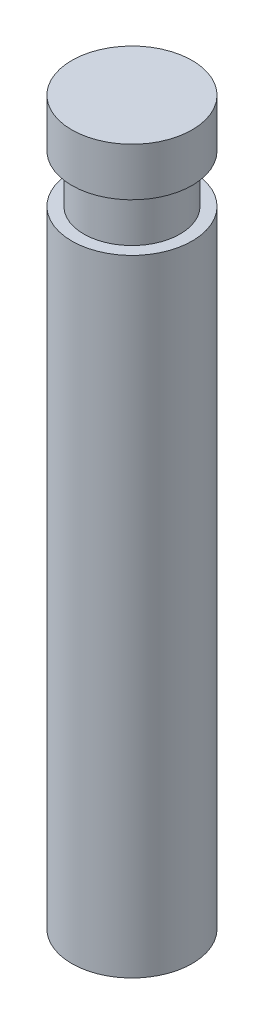
SolidWorks part; units mm, degrees
ref_plane "Front Plane" through (0, 0, 0) normal (0, 0, 1) x (1, 0, 0)
ref_plane "Top Plane" through (0, 0, 0) normal (0, 1, 0) x (1, 0, 0)
ref_plane "Right Plane" through (0, 0, 0) normal (1, 0, 0) x (0, 0, -1)
sketch "Sketch1" plane through (0, 0, 0) normal (0, 1, 0) x (1, 0, 0)
  circle A0 centre (0, 0) radius 1
  circle A1 centre (0, 0) radius 2.5
  circle A2 centre (0, 0) radius 2
extrude "Boss-Extrude1" add sketch "Sketch1" along normal blind 26 contours A1
extrude "Cut-Extrude1" cut sketch "Sketch1<5>" along normal blind 10 contours A0 region at (0, 0, 0)
sketch "Sketch1<5>" plane through (0, 0, 0) normal (0, 1, 0) x (1, 0, 0) same geometry as "Sketch1"
sketch "Sketch3" plane through (0, 26, 0) normal (0, 1, 0) x (1, 0, 0)
  circle A0 centre (0, 0) radius 2
extrude "Boss-Extrude2" add sketch "Sketch3" along normal blind 2
sketch "Sketch4" plane through (0, 28, 0) normal (0, 1, 0) x (1, 0, 0)
  circle A0 centre (0, 0) radius 2.5
extrude "Boss-Extrude3" add sketch "Sketch4" along normal blind 2
